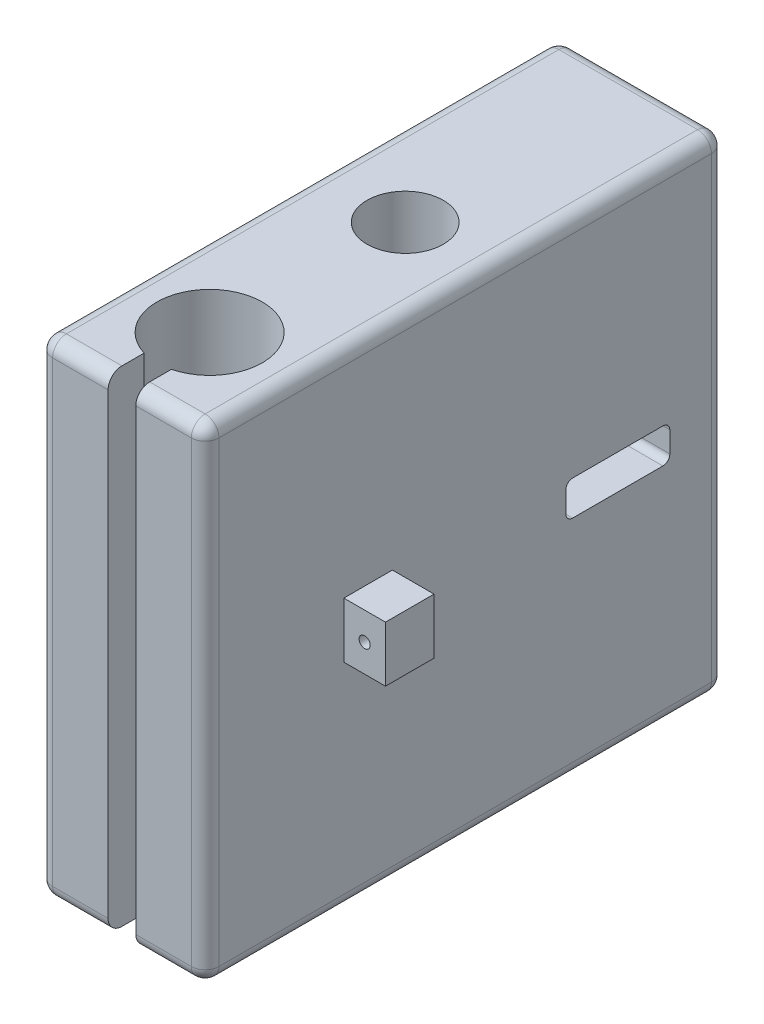
SolidWorks part; units mm, degrees
ref_plane "Front Plane" through (0, 0, 0) normal (0, 0, 1) x (1, 0, 0)
ref_plane "Top Plane" through (0, 0, 0) normal (0, 1, 0) x (1, 0, 0)
ref_plane "Right Plane" through (0, 0, 0) normal (1, 0, 0) x (0, 0, -1)
ref_plane "Plano1" through (-220, 0, 0) normal (1, 0, 0) x (0, 0, -1)
sketch "Esboço1" plane through (-220, 0, 0) normal (1, 0, 0) x (0, 0, -1)
  line L0 (-460.4999, 246.154) -> (-460.4999, 230.354) construction
  line L1 (-465.4999, 248.254) -> (-390.4999, 248.254)
  line L2 (-465.4999, 248.254) -> (-465.4999, 178.254)
  line L3 (-465.4999, 178.254) -> (-390.4999, 178.254)
  line L4 (-390.4999, 248.254) -> (-390.4999, 178.254)
  dimension "D1" = 75
  dimension "D2" = 70
  dimension "D3" = 5
extrude "Ressalto-extrusão1" add sketch "Esboço1" along normal blind 12 and the other way blind 12
sketch "Esboço3" plane through (0, 248.254, 0) normal (0, 1, 0) x (1, 0, 0)
  line L5 (-232, -465.4999) -> (-208, -465.4999) construction
  line L7 (-220, -465.4999) -> (-218, -465.4999)
  line L10 (-218, -465.4999) -> (-218, -460.3692)
  line L11 (-220, -465.4999) -> (-222, -465.4999)
  line L14 (-222, -465.4999) -> (-222, -460.292)
  arc A3 (-218, -460.3692) -> (-222, -460.292) centre (-219.8586, -452.9999) ccw
  circle A8 centre (-219.5085, -425.1499) radius 5.5
  circle A9 centre (-219.5085, -425.1499) radius 5.5
  dimension "D1" = 15.2
  dimension "D3" = 2
  dimension "D4" = 2
  dimension "D2" = 0.5
extrude "Corte-extrusão1" cut sketch "Esboço3" against normal through all
sketch "Esboço4" plane through (0, 0, 390.4999) normal (0, 0, -1) x (-1, 0, 0)
  line L0 (220, 248.254) -> (220, 178.254) construction
  line L1 (232, 248.254) -> (208, 248.254) construction
  line L2 (232, 178.254) -> (208, 178.254) construction
  circle A0 centre (219.8586, 238.254) radius 4.1
  circle A1 centre (219.8586, 188.254) radius 4.1
  dimension "D1" = 8.2
  dimension "D2" = 8.2
extrude "Corte-extrusão2" cut sketch "Esboço4" against normal blind 20
fillet "Filete1" radius 2 14 edges at (-227, 178.254, 465.4999) (-213, 178.254, 465.4999) (-213, 248.254, 465.4999) (-227, 248.254, 465.4999) (-208, 178.254, 427.9999) (-208, 248.254, 427.9999) (-208, 213.254, 465.4999) (-232, 178.254, 427.9999) (-232, 213.254, 465.4999) (-232, 248.254, 427.9999) (-220, 248.254, 390.4999) (-220, 178.254, 390.4999) (-208, 213.254, 390.4999) (-232, 213.254, 390.4999)
sketch "Esboço5" plane through (0, 0, 390.4999) normal (0, 0, -1) x (-1, 0, 0)
  line L8 (213.893, 195.2588) -> (225.893, 195.249)
  line L9 (225.893, 195.249) -> (225.9225, 231.249)
  line L10 (225.9225, 231.249) -> (213.9225, 231.2588)
  line L11 (213.9225, 231.2588) -> (213.893, 195.2588)
  line L12 (213.893, 195.2588) -> (225.893, 195.249)
  line L13 (225.893, 195.249) -> (225.9225, 231.249)
  line L14 (225.9225, 231.249) -> (213.9225, 231.2588)
  line L15 (213.9225, 231.2588) -> (213.893, 195.2588)
  dimension "D1" = 0
extrude "Corte-extrusão3" cut sketch "Esboço5" against normal blind 29
sketch "Esboço6" plane through (-232, 0, 0) normal (-1, 0, 0) x (0, 0, 1)
  line L0 (392.4999, 213.254) -> (463.4999, 213.254) construction
  line L1 (392.4999, 246.254) -> (392.4999, 180.254) construction
  line L2 (463.4999, 180.254) -> (463.4999, 246.254) construction
  line L3 (398.4999, 213.254) -> (413.4999, 213.254) construction
  line L4 (399.4999, 215.754) -> (412.4999, 215.754)
  line L5 (398.4999, 214.754) -> (398.4999, 211.754)
  line L6 (399.4999, 210.754) -> (412.4999, 210.754)
  line L7 (413.4999, 214.754) -> (413.4999, 211.754)
  arc A0 (412.4999, 215.754) -> (413.4999, 214.754) centre (412.4999, 214.754) cw
  arc A1 (412.4999, 210.754) -> (413.4999, 211.754) centre (412.4999, 211.754) ccw
  arc A2 (398.4999, 211.754) -> (399.4999, 210.754) centre (399.4999, 211.754) ccw
  arc A3 (399.4999, 215.754) -> (398.4999, 214.754) centre (399.4999, 214.754) ccw
  point P14 (413.4999, 215.754)
  point P17 (413.4999, 210.754)
  point P22 (398.4999, 215.754)
  dimension "D4" = 1
  dimension "D1" = 5
  dimension "D2" = 15
  dimension "D3" = 6
extrude "Corte-extrusão4" cut sketch "Esboço6" against normal blind 28
sketch "Esboço7" plane through (-208, 0, 0) normal (1, 0, 0) x (0, 0, -1)
  line L0 (-463.4999, 246.254) -> (-463.4999, 180.254) construction
  line L1 (-445.4999, 217.254) -> (-438.4999, 217.254)
  line L2 (-445.4999, 217.254) -> (-445.4999, 209.254)
  line L3 (-445.4999, 209.254) -> (-438.4999, 209.254)
  line L4 (-438.4999, 217.254) -> (-438.4999, 209.254)
  line L5 (-465.4999, 180.254) -> (-465.4999, 246.254) construction
  point P6 (-463.4999, 213.254)
  point P7 (-445.4999, 213.254)
  dimension "D1" = 7
  dimension "D2" = 8
  dimension "D3" = 20
extrude "Ressalto-extrusão2" add sketch "Esboço7" along normal blind 6 and the other way blind 30
ref_point "Ponto1"
sketch "Esboço9" plane through (0, 0, 445.4999) normal (0, 0, 1) x (1, 0, 0)
  line L0 (-205, 217.254) -> (-205, 209.254) construction
  line L3 (-208, 217.254) -> (-202, 217.254) construction
  line L6 (-208, 209.254) -> (-202, 209.254) construction
  line L7 (-208, 213.254) -> (-202, 213.254) construction
  line L8 (-208, 246.254) -> (-208, 180.254) construction
  line L9 (-202, 217.254) -> (-202, 209.254) construction
hole_wizard "Broca de rosquear para tarraxa de M2x0.41" positions "Esboço13" profile "Esboço14" hole size "M2x0.4" standard "Ansi Metric" end condition through all
sketch "Esboço13" plane through (0, 0, 445.4999) normal (0, 0, 1) x (1, 0, 0)
  line L0 (-205, 217.254) -> (-205, 209.254) construction
  point P0 (-205, 213.254)
sketch "Esboço14" plane through (-205, 213.254, 445.4999) normal (1, 0, 0) x (0, -1, 0)
  line L0 (0, 0) -> (0, 55)
  line L1 (0, 55) -> (0.8, 55)
  line L2 (0.8, 55) -> (0.8, 0)
  line L5 (0.8, 0) -> (0, 0)
  line L11 (0, -6.35) -> (0, 107.95) construction
  dimension "Thru Hole Dia." = 1.6
  dimension "Thru Hole Depth" = 55
sketch "Esboço15" plane through (0, 0, 445.4999) normal (0, 0, 1) x (1, 0, 0)
  line L0 (-235, 217.254) -> (-235, 209.254) construction
  line L1 (-238, 217.254) -> (-232, 217.254) construction
  line L2 (-238, 209.254) -> (-232, 209.254) construction
  line L3 (-238, 213.254) -> (-232, 213.254) construction
  line L4 (-238, 217.254) -> (-238, 209.254) construction
  line L5 (-232, 180.254) -> (-232, 246.254) construction
hole_wizard "Broca de rosquear para tarraxa de M2x0.42" positions "Esboço16" profile "Esboço17" hole size "M2x0.4" standard "Ansi Metric" end condition through all
sketch "Esboço16" plane through (0, 0, 445.4999) normal (0, 0, 1) x (1, 0, 0)
  line L0 (-235, 217.254) -> (-235, 209.254) construction
  point P0 (-235, 213.254)
sketch "Esboço17" plane through (-235, 213.254, 445.4999) normal (1, 0, 0) x (0, -1, 0)
  line L0 (0, 0) -> (0, 55)
  line L1 (0, 55) -> (0.8, 55)
  line L2 (0.8, 55) -> (0.8, 0)
  line L5 (0.8, 0) -> (0, 0)
  line L11 (0, -6.35) -> (0, 107.95) construction
  dimension "Thru Hole Dia." = 1.6
  dimension "Thru Hole Depth" = 55
